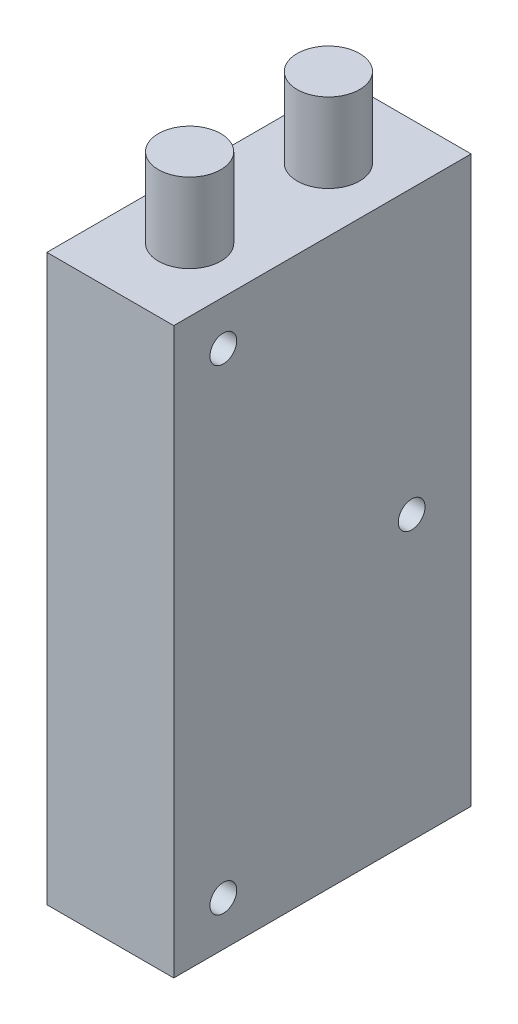
SolidWorks part; units mm, degrees
ref_plane "Front Plane" through (0, 0, 0) normal (0, 0, 1) x (1, 0, 0)
ref_plane "Top Plane" through (0, 0, 0) normal (0, 1, 0) x (1, 0, 0)
ref_plane "Right Plane" through (0, 0, 0) normal (1, 0, 0) x (0, 0, -1)
sketch "Case Sketch" plane through (0, 0, 0) normal (1, 0, 0) x (0, 0, -1)
  line L0 (87, -28.5) -> (87, 28.5)
  line L1 (87, 28.5) -> (57, 28.5)
  line L2 (57, 28.5) -> (57, -28.5)
  line L3 (57, -28.5) -> (87, -28.5)
  circle A0 centre (62, -24) radius 1.35
  circle A1 centre (62, 24) radius 1.35
  circle A2 centre (81, 0) radius 1.35
extrude "Case" add sketch "Case Sketch" against normal blind 12.8
ref_axis "Engine Axis" through (0.64, 0, 0) along (-1, 0, 0)
sketch "Ports Sketch" plane through (0, 0, 0) normal (0, 1, 0) x (1, 0, 0)
  circle A0 centre (-6.4, 65) radius 3.15
  circle A1 centre (-6.4, 79) radius 3.15
extrude "Ports" add sketch "Ports Sketch" along normal blind 8 from offset 28.5
